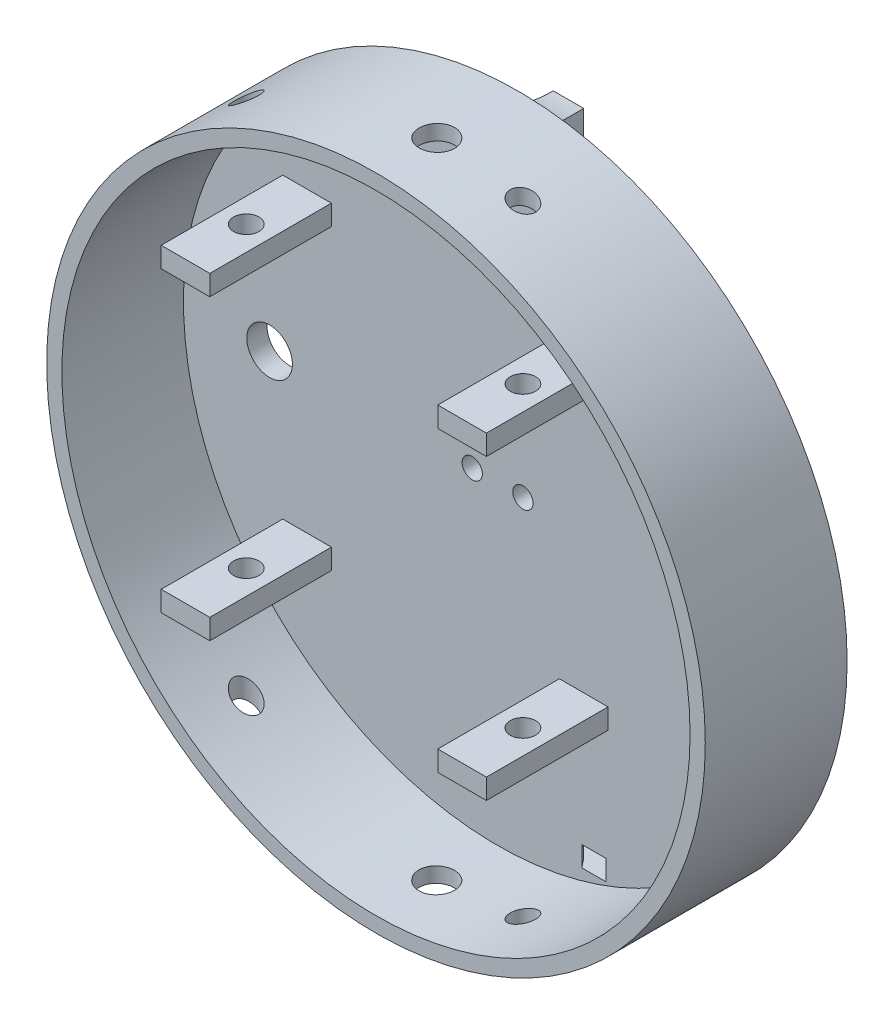
SolidWorks part; units mm, degrees
ref_plane "Alzado" through (0, 0, 0) normal (0, 0, 1) x (1, 0, 0)
ref_plane "Planta" through (0, 0, 0) normal (0, 1, 0) x (1, 0, 0)
ref_plane "Vista lateral" through (0, 0, 0) normal (1, 0, 0) x (0, 0, -1)
sketch "Croquis1" plane through (0, 0, 0) normal (0, 0, 1) x (1, 0, 0)
  line L0 (10, 20) -> (-10, 20) construction
  circle A0 centre (0, 0) radius 32.5
  circle A1 centre (-2.5, 0) radius 1
  circle A2 centre (2.5, 0) radius 1
  circle A3 centre (0, 20) radius 1
  circle A4 centre (10, 20) radius 1
  circle A5 centre (-10, 20) radius 1
  point P9 (0, 20)
  dimension "D1" = 65
  dimension "D4" = 2
  dimension "D7" = 2
  dimension "D2" = 2.5
  dimension "D3" = 2.5
  dimension "D5" = 20
  dimension "D6" = 20
extrude "Saliente-Extruir1" add sketch "Croquis1" along normal blind 2
sketch "Croquis2" plane through (0, 0, 2) normal (0, 0, 1) x (1, 0, 0)
  line L0 (-21.2, -15.7) -> (-16.4, -15.7)
  line L1 (10.9, -15.7) -> (6.1, -15.7)
  line L2 (-21.2, -15.7) -> (-21.2, -13.7)
  line L3 (-21.2, -13.7) -> (-16.4, -13.7)
  line L4 (-16.4, -13.7) -> (-16.4, -15.7)
  line L5 (6.1, -15.7) -> (6.1, -13.7)
  line L6 (6.1, -13.7) -> (10.9, -13.7)
  line L7 (10.9, -13.7) -> (10.9, -15.7)
  line L8 (6.1, -15.7) -> (10.9, -15.7)
  line L9 (0, 0) -> (12.8027, 0) construction
  line L10 (10.9, 13.7) -> (10.9, 15.7)
  line L11 (10.9, 15.7) -> (6.1, 15.7)
  line L12 (6.1, 13.7) -> (10.9, 13.7)
  line L13 (6.1, 15.7) -> (6.1, 13.7)
  line L14 (-16.4, 13.7) -> (-16.4, 15.7)
  line L15 (-21.2, 15.7) -> (-16.4, 15.7)
  line L16 (-21.2, 15.7) -> (-21.2, 13.7)
  line L17 (-21.2, 13.7) -> (-16.4, 13.7)
  point P2 (0, -15.7)
  point P3 (-16.4, -15.7)
  point P13 (8.5, -15.7)
  point P16 (8.5, 15.7)
  dimension "D1" = 32.1
  dimension "D2" = 10.9
  dimension "D3" = 15.7
  dimension "D4" = 4.8
  dimension "D5" = 4.8
  dimension "D6" = 2
  dimension "D7" = 2
extrude "Saliente-Extruir2" add sketch "Croquis2" along normal blind 12 contours L7 L6 L5 L1 | L4 L3 L2 L0 | L16 L17 L14 L15 | L11 L13 L12 L10 region at (-18.8, -14.7, 2) region at (8.5, -14.7, 2) region at (8.5, 14.7, 2) region at (-18.8, 14.7, 2)
sketch "Croquis3" plane through (0, -15.7, 0) normal (0, -1, 0) x (1, 0, 0)
  line L0 (-18.8, 14) -> (-18.8, 2) construction
  line L1 (-21.2, 14) -> (-16.4, 14) construction
  line L2 (-21.2, 2) -> (-16.4, 2) construction
  line L3 (8.5, 14) -> (8.5, 2) construction
  line L4 (10.9, 14) -> (6.1, 14) construction
  line L5 (10.9, 2) -> (6.1, 2) construction
  circle A0 centre (-18.8, 8) radius 1.25
  circle A1 centre (8.5, 8) radius 1.25
  dimension "D1" = 2.5
extrude "Cortar-Extruir1" cut sketch "Croquis3" against normal up to surface (31.4 mm away) up to face at (8.5, 15.7, 8)
ref_plane "Plano1" through (0, -32.5, 0) normal (0, -1, 0) x (-1, 0, 0)
ref_plane "Plano2" through (0, -28.75, 0) normal (0, -1, 0) x (-1, 0, 0)
sketch "Croquis5" plane through (0, -28.75, 0) normal (0, -1, 0) x (-1, 0, 0)
  line L0 (-8.5, -8) -> (18.8, -8) construction
  line L1 (0, 0) -> (0, -8) construction
  line L2 (-32.5, -2) -> (32.5, -2) construction
  line L3 (-10.68, -2) -> (-8.3104, -2)
  line L4 (32.5, 0) -> (-32.5, 0) construction
  line L5 (9.277, 0) -> (6.408, 0)
  line L6 (8.3104, -2) -> (10.68, -2)
  line L7 (-6.408, 0) -> (-9.277, 0)
  arc A0 (-9.277, 0) -> (-10.68, -2) centre (0, -8) ccw
  arc A1 (-6.408, 0) -> (-8.3104, -2) centre (0, -8) ccw
  arc A2 (10.68, -2) -> (9.277, 0) centre (0, -8) ccw
  arc A3 (8.3104, -2) -> (6.408, 0) centre (0, -8) ccw
  dimension "D1" = 24.5
  dimension "D2" = 20.5
extrude "Cortar-Extruir3" cut sketch "Croquis5" against normal blind 2
mirror "Simetría1" about plane through (0, 0, 0) normal (0, 1, 0) of "Cortar-Extruir3"
sketch "Croquis6" plane through (0, 0, 0) normal (0, 0, -1) x (-1, 0, 0)
  circle A0 centre (-22.5, 12.5) radius 2.25
  circle A1 centre (-22.5, -12.5) radius 2.25
  circle A2 centre (22.5, 0) radius 2.25
  dimension "D1" = 4.5
  dimension "D2" = 4.5
  dimension "D3" = 4.5
  dimension "D4" = 45
  dimension "D5" = 22.5
  dimension "D6" = 25
  dimension "D7" = 12.5
extrude "Cortar-Extruir4" cut sketch "Croquis6" against normal blind 2.5
sketch "Croquis7" plane through (0, 0, 2) normal (0, 0, 1) x (1, 0, 0)
  circle A2 centre (0, 0) radius 32.5 construction
  circle A9 centre (0, 0) radius 32.5
  circle A11 centre (0, 0) radius 31
  dimension "D1" = 1.5
extrude "Saliente-Extruir3" add sketch "Croquis7" along normal blind 12
ref_plane "Plano3" through (0, -32.5, 0) normal (0, -1, 0) x (-1, 0, 0)
sketch "Croquis8" plane through (0, -32.5, 0) normal (0, -1, 0) x (-1, 0, 0)
  circle A0 centre (-8.5, -8) radius 1.25 construction
  circle A1 centre (-8.5, -8) radius 1.25
  circle A2 centre (18.8, -8) radius 1.25 construction
  circle A3 centre (18.8, -8) radius 1.25
  circle A4 centre (0, -8) radius 1.75
  dimension "D1" = 3.5
extrude "Cortar-Extruir5" cut sketch "Croquis8" against normal blind 70
sketch "Sketch1" plane through (0, 0, 0) normal (0, 0, -1) x (-1, 0, 0)
  line L0 (6.408, 26.75) -> (6.408, 28.75) construction
  line L1 (-1.502, 29.25) -> (1.498, 29.25)
  line L2 (-1.502, 29.25) -> (-1.502, 26.25)
  line L3 (-1.502, 26.25) -> (1.498, 26.25)
  line L4 (1.498, 29.25) -> (1.498, 26.25)
  line L5 (-1.502, 29.25) -> (1.498, 26.25) construction
  line L6 (-1.502, 26.25) -> (1.498, 29.25) construction
  line L7 (0, 0) -> (-11.4103, 0) construction
  line L8 (-1.502, -26.25) -> (1.498, -29.25) construction
  line L9 (-1.502, -29.25) -> (1.498, -26.25) construction
  line L10 (1.498, -29.25) -> (1.498, -26.25)
  line L11 (-1.502, -26.25) -> (1.498, -26.25)
  line L12 (-1.502, -29.25) -> (-1.502, -26.25)
  line L13 (-1.502, -29.25) -> (1.498, -29.25)
  line L14 (-6.408, -26.75) -> (-6.408, -28.75) construction
  point P0 (-0.002, 27.75)
  point P8 (6.408, 27.75)
  point P15 (-0.002, -27.75)
  dimension "D1" = 4.91
  dimension "D2" = 3
  dimension "D3" = 3
  dimension "D4" = 4.906
extrude "Boss-Extrude1" add sketch "Sketch1" along normal blind 5
fillet "Fillet1" radius 2 6 edges at (1.502, 27.75, 0) (-1.498, -27.75, 0) (0.002, 26.25, 0) (0.002, 29.25, 0) (0.002, -26.25, 0) (0.002, -29.25, 0) second distance 5 first distance on face at (0.002, 27.75, 0)
sketch "Sketch2" plane through (0, 0, 2) normal (0, 0, 1) x (1, 0, 0)
  line L1 (-10.68, -26.75) -> (-5.6668, -26.75)
  line L2 (-10.68, -26.75) -> (-10.68, -28.75)
  line L3 (-10.68, -28.75) -> (-5.6668, -28.75)
  line L4 (-5.6668, -26.75) -> (-5.6668, -28.75)
  line L5 (10.68, 26.75) -> (5.4941, 26.75)
  line L6 (10.68, 26.75) -> (10.68, 28.75)
  line L7 (10.68, 28.75) -> (5.4941, 28.75)
  line L8 (5.4941, 26.75) -> (5.4941, 28.75)
extrude "Tapon" add sketch "Sketch2" against normal up to surface (2 mm away) up to face at (1.002, 26, 0)
equation "\"D2@Croquis6\"=\"D1@Croquis6\""
equation "\"D3@Croquis6\"=\"D1@Croquis6\""
equation "\"D5@Croquis6\"=\"D4@Croquis6\"/2"
equation "\"D7@Croquis6\"=\"D6@Croquis6\"/2"
